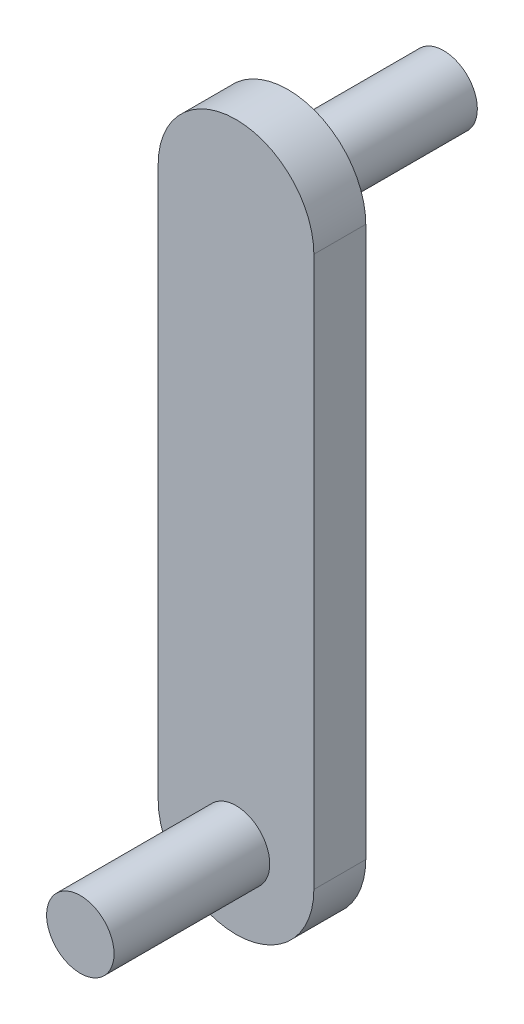
SolidWorks part; units mm, degrees
ref_plane "Front Plane" through (0, 0, 0) normal (0, 0, 1) x (1, 0, 0)
ref_plane "Top Plane" through (0, 0, 0) normal (0, 1, 0) x (1, 0, 0)
ref_plane "Right Plane" through (0, 0, 0) normal (1, 0, 0) x (0, 0, -1)
sketch "Sketch1" plane through (0, 0, 0) normal (0, 0, 1) x (1, 0, 0)
  line L0 (0, 0) -> (0, -53) construction
  line L1 (7.5, 0) -> (7.5, -53)
  line L2 (-7.5, 0) -> (-7.5, -53)
  arc A0 (7.5, 0) -> (-7.5, 0) centre (0, 0) ccw
  arc A1 (-7.5, -53) -> (7.5, -53) centre (0, -53) ccw
  circle A2 centre (0, 0) radius 3.25
  circle A3 centre (0, -53) radius 3.25
  point P3 (0, -26.5)
  dimension "D2" = 6.5
  dimension "D3" = 7.5
  dimension "D1" = 53
extrude "Boss-Extrude1" add sketch "Sketch1" along normal mid plane 5 contours A2 | A3 | L2 A1 L1 A0 A2 A3 region at (0, -26.5, 0) region at (0, 0, 0) region at (0, -53, 0)
extrude "Boss-Extrude2" add sketch "Sketch1<3>" against normal blind 17.5 contours A2
sketch "Sketch1<3>" plane through (0, 0, 0) normal (0, 0, 1) x (1, 0, 0) same geometry as "Sketch1"
extrude "Boss-Extrude3" add sketch "Sketch1<4>" along normal blind 17.5 contours A3
sketch "Sketch1<4>" plane through (0, 0, 0) normal (0, 0, 1) x (1, 0, 0) same geometry as "Sketch1"
